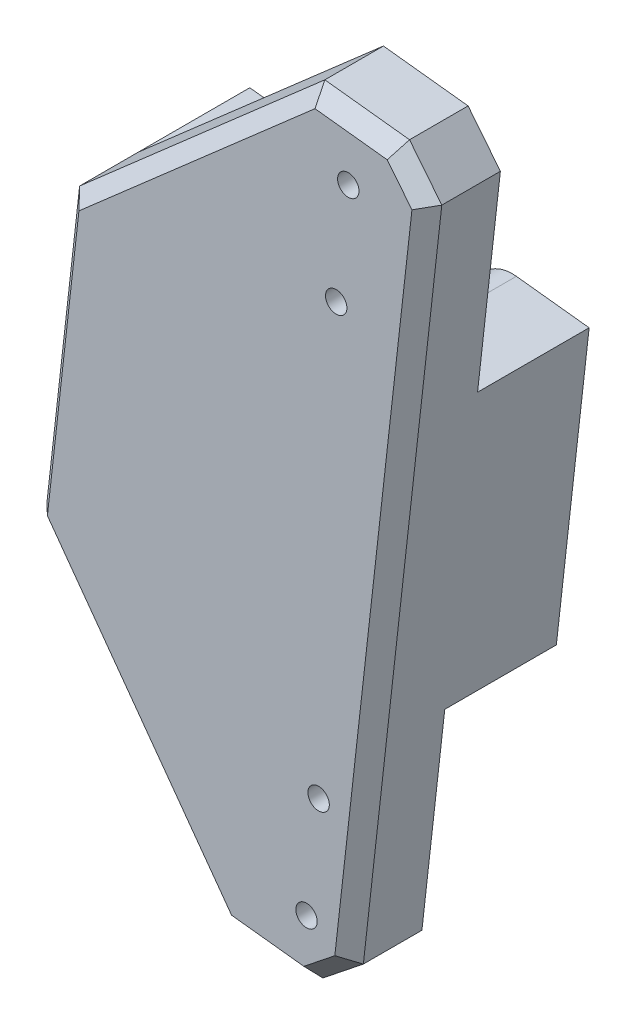
SolidWorks part; units mm, degrees
note: The reader was unsure of these and kept them because the rebuilt part matched: shared geometry of "Sketch7<4>".
material "PET"
ref_plane "Front Plane" through (0, 0, 0) normal (0, 0, 1) x (1, 0, 0)
ref_plane "Top Plane" through (0, 0, 0) normal (0, 1, 0) x (1, 0, 0)
ref_plane "Right Plane" through (0, 0, 0) normal (1, 0, 0) x (0, 0, -1)
sketch "Sketch1" plane through (0, 0, 0) normal (0, 0, 1) x (1, 0, 0)
  line L1 (8.8189, -165.9134) -> (7.3555, -203.4312) construction
  line L2 (1.4166, -196.7013) -> (4.2595, -171.4608)
  line L3 (1.4166, -196.7013) -> (11.9149, -197.8837)
  line L4 (4.2595, -171.4608) -> (14.7577, -172.6433)
  line L5 (11.9149, -197.8837) -> (14.7577, -172.6433)
  line L6 (1.4166, -196.7013) -> (14.7577, -172.6433) construction
  line L7 (4.2595, -171.4608) -> (11.9149, -197.8837) construction
  line L8 (16.771, -154.7681) -> (15.9834, -161.7615) construction
  point P1 (8.0872, -184.6723)
  dimension "D1" = 25.4
extrude "Boss-Extrude1" add sketch "Sketch1" along normal up to surface (9.6774 mm away)
sketch "Sketch2" plane through (0, 0, 9.6774) normal (0, 0, 1) x (1, 0, 0)
  line L0 (14.7577, -172.6433) -> (1.4166, -196.7013) construction
  line L1 (4.2595, -171.4608) -> (14.7577, -172.6433) construction
  line L2 (14.7577, -172.6433) -> (11.9149, -197.8837) construction
  line L3 (1.4166, -196.7013) -> (4.2595, -171.4608) construction
  line L4 (8.0872, -184.6723) -> (11.8443, -151.314) construction
  line L5 (8.1331, -150.896) -> (16.5887, -151.8483) construction
  line L6 (-0.9191, -217.4394) -> (6.5952, -150.7227)
  line L7 (-0.9191, -217.4394) -> (9.5792, -218.6218)
  line L8 (6.5952, -150.7227) -> (17.0935, -151.9052)
  line L9 (9.5792, -218.6218) -> (17.0935, -151.9052)
  line L10 (-0.9191, -217.4394) -> (17.0935, -151.9052) construction
  line L11 (6.5952, -150.7227) -> (9.5792, -218.6218) construction
extrude "Boss-Extrude2" add sketch "Sketch2" along normal blind 6.35
hole_wizard "#0 Clearance Hole1" positions "Sketch3" profile "Sketch4" hole size "#0" standard "ANSI Inch" end condition up to next
sketch "Sketch3" plane through (0, 0, 16.0274) normal (0, 0, 1) x (1, 0, 0)
  point P0 (9.8977, -156.3346)
  point P3 (8.8501, -165.6357)
  point P6 (7.3243, -203.7088)
  point P9 (6.2767, -213.0099)
sketch "Sketch4" plane through (9.8977, -156.3346, 16.0274) normal (1, 0, 0) x (0, -1, 0)
  line L0 (0, 0) -> (0, 6.35)
  line L1 (0, 6.35) -> (0.9271, 6.35)
  line L2 (0.9271, 6.35) -> (0.9271, 0)
  line L5 (0.9271, 0) -> (0, 0)
  line L11 (0, -6.35) -> (0, 107.95) construction
  dimension "Thru Hole Dia." = 1.8542
  dimension "Thru Hole Depth" = 6.35
hole_wizard "Hole1" positions "Sketch5" profile "Sketch6" legacy
sketch "Sketch5" plane through (0, 0, 9.6774) normal (0, 0, -1) x (-1, 0, 0)
  point P0 (-9.8977, -156.3346)
  point P3 (-8.8501, -165.6357)
  point P6 (-7.3243, -203.7088)
  point P9 (-6.2767, -213.0099)
sketch "Sketch6" plane through (9.8977, -156.3346, 9.6774) normal (1, 0, 0) x (0, 1, 0)
  line L0 (0, 0) -> (0, 2.921)
  line L1 (0, 2.921) -> (1.4986, 2.921)
  line L2 (1.4986, 2.921) -> (1.6383, 0)
  line L3 (1.6383, 0) -> (0, 0)
  line L4 (0, 110) -> (0, -10) construction
  dimension "Minor Diameter" = 2.9972
  dimension "Depth" = 2.921
  dimension "Major Diameter" = 3.2766
sketch "Sketch7" plane through (0, 0, 16.0274) normal (0, 0, 1) x (1, 0, 0)
  line L1 (4.2595, -171.4608) -> (1.4166, -196.7013)
  line L2 (4.2595, -171.4608) -> (-14.6708, -169.3287)
  line L3 (1.4166, -196.7013) -> (-17.5137, -194.5691)
  line L4 (-14.6708, -169.3287) -> (-17.5137, -194.5691)
  line L5 (-14.6708, -169.3287) -> (6.5952, -150.7227)
  line L6 (6.5952, -150.7227) -> (-0.9191, -217.4394)
  line L7 (-0.9191, -217.4394) -> (-17.5137, -194.5691)
  line M11 (6.5952, -150.7227) -> (-0.9191, -217.4394)
  dimension "D1" = 19.05
extrude "Boss-Extrude3" add sketch "Sketch7" against normal up to surface (6.35 mm away) contours L7 L3 M11 | L5 L2 M11 up to face at (5.4979, -207.6615, 9.6774)
extrude "Boss-Extrude4" add sketch "Sketch7<4>" against normal up to surface (16.0274 mm away) contours L2 L4 L3 M11 up to face at (8.0872, -184.6723, 0)
sketch "Sketch7<4>" plane through (0, 0, 16.0274) normal (0, 0, 1) x (1, 0, 0) same geometry as "Sketch7"
sketch "Sketch10" [suppressed] plane through (0, 0, 0) normal (0, 0, -1) x (-1, 0, 0)
  line L0 (2.7994, -196.2264) -> (-0.0435, -170.986) construction
  line L1 (17.5137, -194.5691) -> (-11.9149, -197.8837) construction
  line L2 (-14.7577, -172.6433) -> (14.6708, -169.3287) construction
  line L3 (4.6891, -170.453) -> (7.5319, -195.6934)
  line L4 (4.6891, -170.453) -> (-4.776, -171.519)
  line L5 (7.5319, -195.6934) -> (-1.9332, -196.7594)
  line L6 (-4.776, -171.519) -> (-1.9332, -196.7594)
  line L7 (4.6891, -170.453) -> (-1.9332, -196.7594) construction
  line L8 (7.5319, -195.6934) -> (-4.776, -171.519) construction
  point P7 (1.378, -183.6062)
  dimension "D1" = 9.525
sketch "Sketch11" plane through (-19.0163, -168.8393, 0) normal (0.1119, 0.9937, 0) x (0.9937, -0.1119, 0)
  line L0 (33.9876, 0) -> (4.373, 0) construction
  line L1 (24.4626, -3.0498) -> (24.4626, 3.0498)
  line L2 (24.4626, 3.0498) -> (19.1803, 6.0995)
  line L3 (19.1803, 6.0995) -> (13.898, 3.0498)
  line L4 (13.898, 3.0498) -> (13.898, -3.0498)
  line L5 (13.898, -3.0498) -> (19.1803, -6.0995)
  line L6 (19.1803, -6.0995) -> (24.4626, -3.0498)
  line L7 (33.9876, -9.6774) -> (33.9876, 0) construction
  circle A0 centre (19.1803, 0) radius 5.2823 construction
  dimension "D1" = 9.525
extrude "Cut-Extrude2" cut sketch "Sketch11" against normal up to next
hole_wizard "#6 Clearance Hole1" positions "Sketch12" profile "Sketch13" hole size "#6" standard "ANSI Inch"
sketch "Sketch12" plane through (0, 0, 0) normal (0, 0, -1) x (-1, 0, 0)
  line L0 (-13.3363, -185.2635) -> (-3.8712, -184.1974) construction
  line L1 (-11.9149, -197.8837) -> (-14.7577, -172.6433) construction
  line L2 (-5.2926, -171.5772) -> (-2.4498, -196.8176) construction
  line L3 (-3.8712, -184.1974) -> (6.6271, -183.015) construction
  line L4 (8.0485, -195.6352) -> (5.2057, -170.3948) construction
  line L5 (6.6271, -183.015) -> (16.0922, -181.9489) construction
  line L6 (17.5137, -194.5691) -> (14.6708, -169.3287) construction
  point P16 (-8.6038, -184.7304)
  point P18 (11.3597, -182.482)
sketch "Sketch13" plane through (-11.3597, -182.482, 0) normal (1, 0, 0) x (0, 1, 0)
  line L0 (0, 0) -> (0, 11.4534)
  line L1 (0, 11.4534) -> (2.1526, 10.16)
  line L2 (2.1526, 10.16) -> (2.1526, 0)
  line L5 (2.1526, 0) -> (0, 0)
  line L10 (0, 11.4534) -> (-2.1527, 10.16) construction
  line L11 (0, -6.35) -> (0, 107.95) construction
  dimension "Hole Dia." = 4.3053
  dimension "Hole Depth" = 10.16
  dimension "Drill Angle" = 118
hole_wizard "Hole2" positions "Sketch14" profile "Sketch15" legacy
sketch "Sketch14" plane through (0, 0, 0) normal (0, 0, -1) x (-1, 0, 0)
  point P0 (-8.6038, -184.7304)
  point P3 (11.3597, -182.482)
sketch "Sketch15" plane through (8.6038, -184.7304, 0) normal (1, 0, 0) x (0, 1, 0)
  line L0 (0, 0) -> (0, 3.81)
  line L1 (0, 3.81) -> (2.5273, 3.81)
  line L2 (2.5273, 3.81) -> (2.6543, 0)
  line L3 (2.6543, 0) -> (0, 0)
  line L4 (0, 110) -> (0, -10) construction
  dimension "Minor Diameter" = 5.0546
  dimension "Depth" = 3.81
  dimension "Major Diameter" = 5.3086
chamfer "Chamfer4" distance 3.175 angle 45 2 edges at (9.5792, -218.6218, 12.8524) (17.0935, -151.9052, 12.8524)
chamfer "Chamfer3" distance 1.27 angle 45 8 edges at (-4.0378, -160.0257, 16.0274) (10.2668, -151.1363, 16.0274) (13.3363, -185.2635, 16.0274) (2.7525, -217.8529, 16.0274) (-9.2164, -206.0042, 16.0274) (-16.0922, -181.9489, 16.0274) (15.3383, -153.305, 16.0274) (8.1793, -216.8666, 16.0274)
fillet "Fillet1" radius 3.175 8 edges at (5.2926, -171.5772, 1.5249) (2.668, -171.2816, 4.5746) (-2.5811, -170.6904, 4.5746) (-5.2057, -170.3948, 1.5249) (-8.0485, -195.6352, 1.5249) (-5.4239, -195.9308, 4.5746) (-0.1748, -196.522, 4.5746) (2.4498, -196.8176, 1.5249)
